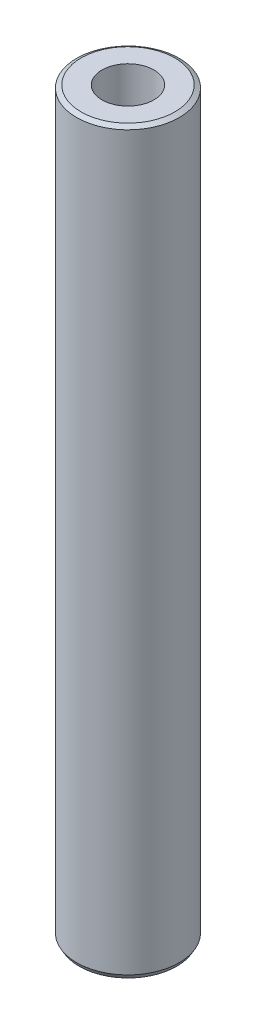
SolidWorks part; units mm, degrees
ref_plane "Front Plane" through (0, 0, 0) normal (0, 0, 1) x (1, 0, 0)
ref_plane "Top Plane" through (0, 0, 0) normal (0, 1, 0) x (1, 0, 0)
ref_plane "Right Plane" through (0, 0, 0) normal (1, 0, 0) x (0, 0, -1)
sketch "Sketch1" plane through (0, 0, 0) normal (0, 1, 0) x (1, 0, 0)
  circle A0 centre (0, 0) radius 32.5
  dimension "SHAFT_OD" = 65
extrude "Boss-Extrude1" add sketch "Sketch1" along normal blind 467.7716
sketch "Sketch2" plane through (0, 0, 0) normal (0, 1, 0) x (1, 0, 0)
  circle A0 centre (0, 0) radius 16.434
  dimension "BORE_D" = 32.868
extrude "Cut-Extrude1" cut sketch "Sketch2" along normal through all
chamfer "Chamfer1" distance 1.6477 angle 60 2 edges at (0, 467.7716, 32.5) (0, 0, 32.5) first distance on face at (0, 467.7716, 32.5) first distance on face at (0, 0, 16.434)
